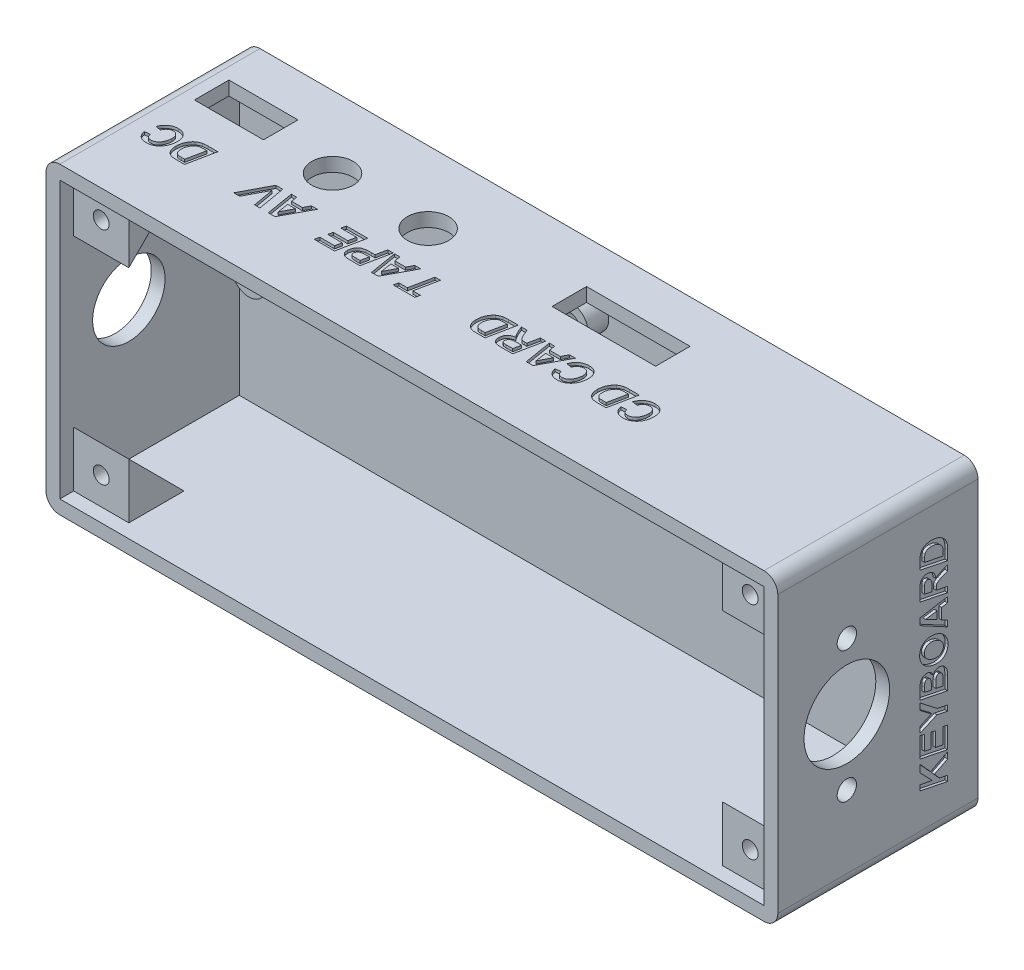
SolidWorks part; units mm, degrees
material "ABS"
ref_plane "Спереди" through (0, 0, 0) normal (0, 0, 1) x (1, 0, 0)
ref_plane "Сверху" through (0, 0, 0) normal (0, 1, 0) x (1, 0, 0)
ref_plane "Справа" through (0, 0, 0) normal (1, 0, 0) x (0, 0, -1)
sketch "Эскиз1" plane through (0, 0, 0) normal (0, 0, 1) x (1, 0, 0)
  line L1 (-53, -22) -> (53, -22)
  line L2 (-53, -22) -> (-53, 22)
  line L3 (-53, 22) -> (53, 22)
  line L4 (53, -22) -> (53, 22)
  line L5 (-53, -22) -> (53, 22) construction
  line L6 (-53, 22) -> (53, -22) construction
  point P0 (0, 0)
  dimension "D1" = 106
  dimension "D2" = 44
extrude "Бобышка-Вытянуть1" add sketch "Эскиз1" along normal blind 3
sketch "Эскиз2" plane through (0, 0, 3) normal (0, 0, 1) x (1, 0, 0)
  line L0 (53, 22) -> (-53, 22) construction
  line L1 (-51, -20) -> (51, -20)
  line L2 (-51, -20) -> (-51, 20)
  line L3 (-51, 20) -> (51, 20)
  line L4 (51, -20) -> (51, 20)
  line L5 (-51, -20) -> (51, 20) construction
  line L6 (-51, 20) -> (51, -20) construction
  line L7 (53, -22) -> (53, 22) construction
  line L9 (-53, -22) -> (53, -22)
  line L10 (-53, -22) -> (-53, 22)
  line L11 (-53, 22) -> (53, 22)
  line L12 (53, -22) -> (53, 22)
  line L13 (-53, -22) -> (53, 22) construction
  line L14 (-53, 22) -> (53, -22) construction
  point P0 (0, 0)
  point P10 (0, 0)
  dimension "D1" = 2
  dimension "D2" = 2
extrude "Бобышка-Вытянуть2" add sketch "Эскиз2" along normal blind 26
sketch "Эскиз3" plane through (0, 0, 3) normal (0, 0, 1) x (1, 0, 0)
  line L0 (51, 20) -> (-51, 20) construction
  line L1 (-46.625, -1.47) -> (46.625, -1.47) construction
  line L2 (-46.625, -1.47) -> (-46.625, 16.18) construction
  line L3 (-46.625, 16.18) -> (46.625, 16.18) construction
  line L4 (46.625, -1.47) -> (46.625, 16.18) construction
  line L5 (-46.625, -1.47) -> (46.625, 16.18) construction
  line L6 (-46.625, 16.18) -> (46.625, -1.47) construction
  circle A0 centre (-46.625, -1.47) radius 2.5
  circle A1 centre (46.625, -1.47) radius 2.5
  circle A2 centre (0.005, 16.18) radius 2.5
  point P0 (0, 0)
  point P13 (0, 7.355)
  dimension "D4" = 5
  dimension "D1" = 93.25
  dimension "D2" = 17.65
  dimension "D3" = 46.63
  dimension "D5" = 3.82
extrude "Бобышка-Вытянуть3" add sketch "Эскиз3" along normal blind 3
sketch "Эскиз4" plane through (0, 0, 6) normal (0, 0, 1) x (1, 0, 0)
  circle A0 centre (-46.625, -1.47) radius 1.15
  circle A1 centre (0.005, 16.18) radius 1.15
  circle A2 centre (46.625, -1.47) radius 1.15
  dimension "D1" = 2.3
extrude "Вырез-Вытянуть1" cut sketch "Эскиз4" against normal blind 5.6
sketch "Эскиз5" plane through (0, 22, 0) normal (0, 1, 0) x (1, 0, 0)
  line L1 (-49.3, -6.2) -> (-39.3, -6.2)
  line L2 (-49.3, -6.2) -> (-49.3, -11.2)
  line L3 (-49.3, -11.2) -> (-39.3, -11.2)
  line L4 (-39.3, -6.2) -> (-39.3, -11.2)
  line L5 (-49.3, -6.2) -> (-39.3, -11.2) construction
  line L6 (-49.3, -11.2) -> (-39.3, -6.2) construction
  line L7 (2.5, -6.2) -> (17.5, -6.2)
  line L8 (2.5, -6.2) -> (2.5, -11.2)
  line L9 (2.5, -11.2) -> (17.5, -11.2)
  line L10 (17.5, -6.2) -> (17.5, -11.2)
  line L11 (2.5, -6.2) -> (17.5, -11.2) construction
  line L12 (2.5, -11.2) -> (17.5, -6.2) construction
  line L13 (53, 0) -> (-53, 0) construction
  line L14 (-53, -29) -> (-53, 0) construction
  circle A0 centre (-30.1, -10.4) radius 3
  circle A1 centre (-16.25, -10.4) radius 3
  point P0 (-44.3, -8.7)
  point P9 (10, -8.7)
  dimension "D5" = 6
  dimension "D2" = 10
  dimension "D3" = 6.2
  dimension "D4" = 5
  dimension "D6" = 13.85
  dimension "D7" = 14.2
  dimension "D8" = 26.25
  dimension "D9" = 10.4
  dimension "D10" = 5
  dimension "D11" = 15
  dimension "D12" = 22.9
extrude "Вырез-Вытянуть2" cut sketch "Эскиз5" against normal up to next
sketch "Эскиз7" plane through (53, 0, 0) normal (1, 0, 0) x (0, 0, -1)
  line L0 (-20, 0) -> (-6.0564, 0) construction
  line L1 (-29, -22) -> (-29, 22) construction
  circle A0 centre (-19, 0) radius 6.2
  circle A1 centre (-19, -9.5) radius 1.4
  circle A2 centre (-19, 9.5) radius 1.4
  dimension "D1" = 12.4
  dimension "D4" = 2.8
  dimension "D2" = 10
  dimension "D3" = 19
extrude "Вырез-Вытянуть3" cut sketch "Эскиз7" against normal up to next
sketch "Эскиз8" plane through (51, 0, 0) normal (-1, 0, 0) x (0, 0, 1)
  line L0 (27, 20) -> (27, 12)
  line L1 (29, 20) -> (3, 20) construction
  line L2 (27, 12) -> (19, 20)
  line L3 (19, 20) -> (27, 20)
  line L4 (29, -20) -> (29, 20) construction
  dimension "D1" = 8
  dimension "D2" = 8
  dimension "D3" = 2
extrude "Бобышка-Вытянуть4" add sketch "Эскиз8" along normal blind 8
sketch "Эскиз9" plane through (0, 0, 27) normal (0, 0, 1) x (1, 0, 0)
  line L0 (43, 12) -> (43, 20) construction
  line L1 (43, 20) -> (51, 20) construction
  line L2 (43, 20) -> (43, 12) construction
  line L3 (43, 12) -> (51, 12) construction
  line L4 (51, 20) -> (51, 12) construction
  line L5 (43, 20) -> (51, 12) construction
  line L6 (43, 12) -> (51, 20) construction
  line L7 (43, 20) -> (51, 20) construction
  circle A0 centre (47, 16) radius 1.15
  point P0 (47, 16)
  dimension "D1" = 2.3
extrude "Вырез-Вытянуть4" cut sketch "Эскиз9" against normal up to next
mirror "Зеркальное отражение1" about plane through (0, 0, 0) normal (0, 1, 0) of "Вырез-Вытянуть4", "Бобышка-Вытянуть4"
mirror "Зеркальное отражение2" about plane through (0, 0, 0) normal (1, 0, 0) of "Вырез-Вытянуть4", "Зеркальное отражение1", "Бобышка-Вытянуть4"
fillet "Скругление1" radius 2 4 edges at (-53, 22, 14.5) (53, 22, 14.5) (53, -22, 14.5) (-53, -22, 14.5)
sketch "Эскиз10" plane through (0, 22, 0) normal (0, 1, 0) x (1, 0, 0)
  line L0 (51, 0) -> (-51, 0) construction
  line L1 (-53, -29) -> (-53, 0) construction
  text T0 "<r180>VA</r>" font "Times New Roman" height 4
  text T1 "<r180>EPAT</r>" font "Times New Roman" height 4
  text T2 "<r180>CD</r>" font "Times New Roman" height 4
  text T3 "<r180>DRAC DC</r>" font "Times New Roman" height 4
  dimension "D1" = 16
  dimension "D2" = 22.5962
  dimension "D3" = 11.2585
  dimension "D4" = 14.4528
  dimension "D5" = 21.8
extrude "Вырез-Вытянуть5" cut sketch "Эскиз10" against normal blind 0.4
sketch "Эскиз11" plane through (53, 0, 0) normal (1, 0, 0) x (0, 0, -1)
  line L0 (-4.4, -16) -> (-4.4, 15) construction
  line L1 (0, -20) -> (0, 20) construction
  line L2 (0, -22) -> (-29, -22) construction
  text T0 "KEYBOARD" font "Arial" height 4
  dimension "D1" = 4.4
  dimension "D2" = 31
  dimension "D3" = 6
extrude "Вырез-Вытянуть6" cut sketch "Эскиз11" against normal blind 0.4
sketch "Эскиз12" plane through (0, 20, 0) normal (0, -1, 0) x (1, 0, 0)
  line L1 (-53, 0) -> (-53, 29) construction
  line L2 (-51, 0) -> (51, 0) construction
  text T0 "© Peter Ukhov 2023" font "Arial" height 6
  dimension "D1" = 16
  dimension "D2" = 14
sketch "Эскиз13" plane through (-53, 0, 0) normal (-1, 0, 0) x (0, 0, 1)
  line L0 (29, 20) -> (29, -20) construction
  circle A0 centre (19, 0) radius 5.25
  dimension "D1" = 10.5
  dimension "D2" = 10
extrude "Вырез-Вытянуть8" cut sketch "Эскиз13" against normal up to next
sketch "Эскиз14" plane through (-53, 0, 0) normal (-1, 0, 0) x (0, 0, 1)
  line L0 (6.2274, 10.1387) -> (6.2274, -12.1287) construction
  text T0 "POWER" font "Arial" height 4
extrude "Вырез-Вытянуть9" cut sketch "Эскиз14" against normal blind 0.4
extrude "Вырез-Вытянуть10" cut sketch "Эскиз12" against normal blind 0.4
equation "\"D1@Эскиз1\"=100+2*2+2"
equation "\"D2@Эскиз1\"=40+2*2"
equation "\"D5@Эскиз3\"=3.42+0.4"
equation "\"D2@Эскиз7\"=14/2+3"
